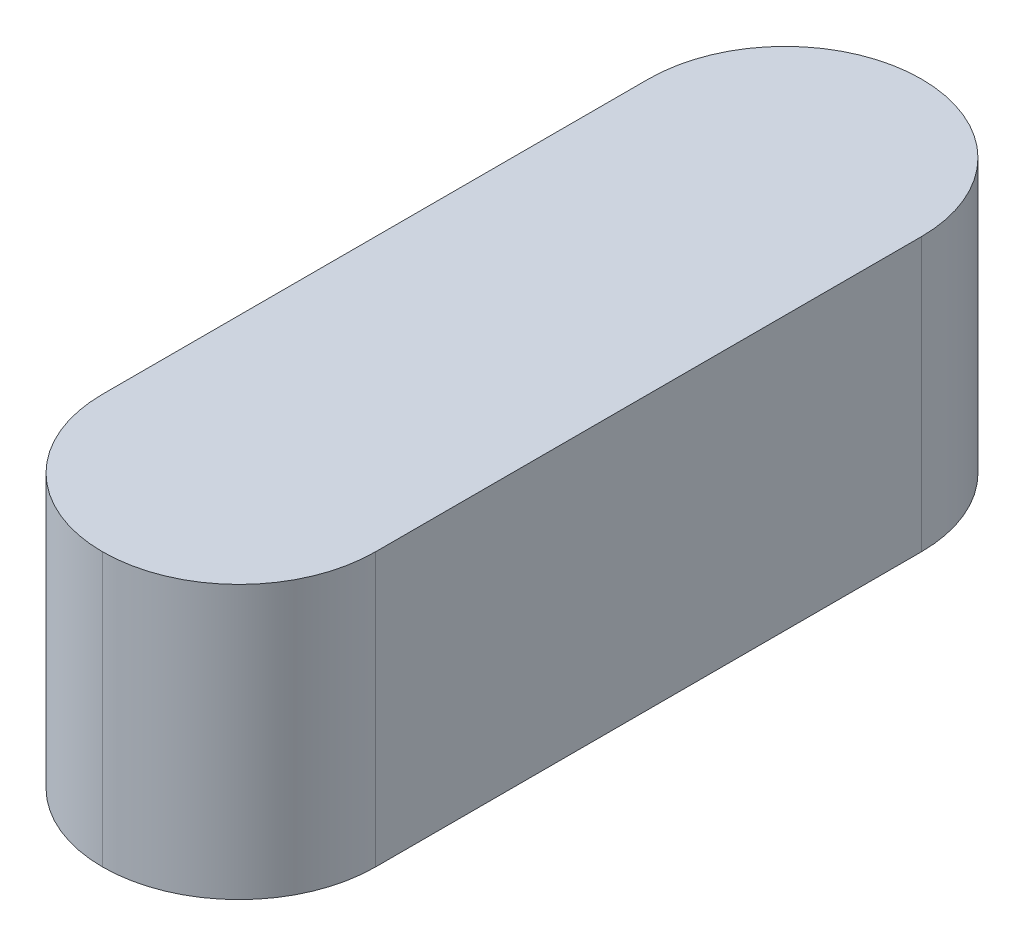
SolidWorks part; units mm, degrees
ref_plane "Front Plane" through (0, 0, 0) normal (0, 0, 1) x (1, 0, 0)
ref_plane "Top Plane" through (0, 0, 0) normal (0, 1, 0) x (1, 0, 0)
ref_plane "Right Plane" through (0, 0, 0) normal (1, 0, 0) x (0, 0, -1)
sketch "Sketch1" plane through (0, 0, 0) normal (0, 0, 1) x (1, 0, 0)
  line L1 (0, 4.795) -> (6, 4.795)
  line L2 (0, 4.795) -> (0, 10.795)
  line L3 (0, 10.795) -> (6, 10.795)
  line L4 (6, 4.795) -> (6, 10.795)
  dimension "D1" = 6
  dimension "D2" = 6
extrude "Extrude1" add sketch "Sketch1" along normal blind 18
fillet "Fillet1" radius 3 4 edges at (0, 7.795, 0) (6, 7.795, 0) (0, 7.795, 18) (6, 7.795, 18)
